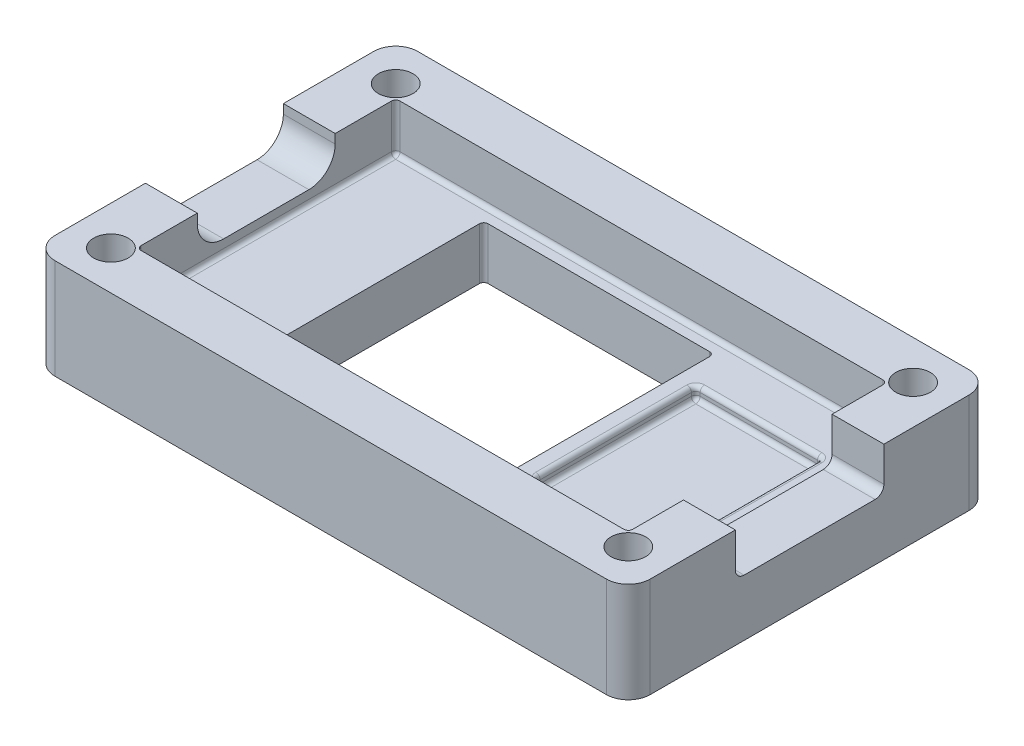
SolidWorks part; units mm, degrees
material "ABS"
ref_plane "Front Plane" through (0, 0, 0) normal (0, 0, 1) x (1, 0, 0)
ref_plane "Top Plane" through (0, 0, 0) normal (0, 1, 0) x (1, 0, 0)
ref_plane "Right Plane" through (0, 0, 0) normal (1, 0, 0) x (0, 0, -1)
sketch "Sketch1" plane through (0, 0, 0) normal (0, 1, 0) x (1, 0, 0)
  line L1 (-17.224, -10.493) -> (17.224, -10.493)
  line L2 (-17.224, -10.493) -> (-17.224, 10.493)
  line L3 (-17.224, 10.493) -> (17.224, 10.493)
  line L4 (17.224, -10.493) -> (17.224, 10.493)
  line L5 (-17.224, -10.493) -> (17.224, 10.493) construction
  line L6 (-17.224, 10.493) -> (17.224, -10.493) construction
  point P0 (0, 0)
  dimension "D1" = 20.986
  dimension "D2" = 34.448
extrude "Boss-Extrude1" add sketch "Sketch1" along normal blind 5.794
sketch "Sketch2" plane through (0, 5.794, 0) normal (0, 1, 0) x (1, 0, 0)
  line L1 (-14.224, -7.493) -> (14.224, -7.493)
  line L2 (-14.224, -7.493) -> (-14.224, 7.493)
  line L3 (-14.224, 7.493) -> (14.224, 7.493)
  line L4 (14.224, -7.493) -> (14.224, 7.493)
  line L5 (-14.224, -7.493) -> (14.224, 7.493) construction
  line L6 (-14.224, 7.493) -> (14.224, -7.493) construction
  point P0 (0, 0)
  dimension "D1" = 14.986
  dimension "D2" = 28.448
extrude "Cut-Extrude1" cut sketch "Sketch2" against normal blind 2.794
fillet "Fillet4" radius 0.254 4 edges at (14.224, 4.397, 7.493) (-14.224, 4.397, 7.493) (14.224, 4.397, -7.493) (-14.224, 4.397, -7.493)
sketch "Sketch3" plane through (17.224, 0, 0) normal (1, 0, 0) x (0, 0, -1)
  line L0 (-10.493, 5.794) -> (10.493, 5.794) construction
  line L1 (-4.2995, 5.794) -> (4.2995, 5.794)
  line L2 (-4.2995, 5.794) -> (-4.2995, 3.2749)
  line L3 (-4.2995, 3.2749) -> (4.2995, 3.2749)
  line L4 (4.2995, 5.794) -> (4.2995, 3.2749)
  line L5 (-10.493, 0) -> (10.493, 0) construction
  point P6 (0, 3.2749)
  point P11 (0, 0)
extrude "Cut-Extrude2" cut sketch "Sketch3" against normal up to surface (3 mm away) up to face at (14.224, 4.397, 0)
sketch "Sketch5" plane through (-17.224, 0, 0) normal (-1, 0, 0) x (0, 0, 1)
  line L0 (-3.9914, 5.794) -> (3.9914, 5.794)
  line L1 (-10.493, 5.794) -> (10.493, 5.794) construction
  line L2 (-10.493, 0) -> (10.493, 0) construction
  line L3 (-3.9914, 3.7403) -> (3.9914, 3.7403)
  line L4 (3.9914, 3.7403) -> (3.9914, 5.794)
  line L5 (-3.9914, 5.794) -> (-3.9914, 3.7403)
  point P4 (0, 5.794)
  point P7 (0, 0)
  point P8 (0, 3.7403)
extrude "Cut-Extrude3" cut sketch "Sketch5" against normal up to surface (3 mm away) up to face at (-14.224, 4.397, 0)
fillet "Fillet1" radius 1.524 2 edges at (-15.724, 3.7403, 3.9914) (-15.724, 3.7403, -3.9914)
fillet "Fillet2" radius 0.508 2 edges at (15.724, 3.2749, -4.2995) (15.724, 3.2749, 4.2995)
fillet "Fillet3" radius 1.27 4 edges at (-17.224, 2.897, -10.493) (-17.224, 2.897, 10.493) (17.224, 2.897, 10.493) (17.224, 2.897, -10.493)
fillet "Fillet5" radius 0.254 8 edges at (-14.1496, 3, 7.4186) (-14.224, 3, 0) (-14.1496, 3, -7.4186) (0, 3, -7.493) (14.1496, 3, -7.4186) (14.224, 3, 0) (14.1496, 3, 7.4186) (0, 3, 7.493)
sketch "Sketch10" plane through (0, 5.794, -5.794) normal (0, -1, 0) x (-1, 0, 0)
  circle A0 centre (-14.9721, 2.4471) radius 1
  circle A2 centre (14.9721, 2.4471) radius 1
  circle A3 centre (14.9721, -14.0351) radius 1
  circle A4 centre (-14.9721, -14.0351) radius 1
  circle A8 centre (14.9721, -14.0351) radius 1 construction
  circle A9 centre (14.9721, 2.4471) radius 1 construction
  circle A10 centre (-14.9721, 2.4471) radius 1 construction
  circle A11 centre (-14.9721, -14.0351) radius 1 construction
extrude "Cut-Extrude4" cut sketch "Sketch10" along normal blind 4.54
sketch "Sketch11" plane through (0, 0, 0) normal (0, -1, 0) x (1, 0, 0)
  line L0 (4.499, -6.1851) -> (-7.821, -6.1851) construction
  line L1 (-7.821, -6.1851) -> (4.499, -6.1851) construction
  line L2 (-7.821, -6.1851) -> (-7.821, 6.1349) construction
  line L3 (-7.821, 6.1349) -> (4.499, 6.1349) construction
  line L4 (4.499, -6.1851) -> (4.499, 6.1349) construction
  line L5 (4.499, 6.1349) -> (4.499, -6.1851) construction
  line L6 (-7.821, -6.1851) -> (4.499, 6.1349) construction
  line L7 (-8.321, -6.6851) -> (4.999, -6.6851)
  line L8 (-8.321, -6.6851) -> (-8.321, 6.6349)
  line L9 (-8.321, 6.6349) -> (4.999, 6.6349)
  line L10 (4.999, -6.6851) -> (4.999, 6.6349)
  line L11 (4.999, 6.6349) -> (-8.321, -6.6851) construction
  point P12 (-1.661, -0.0251)
  point P13 (-1.661, -0.0251)
  dimension "D1" = 0.5
extrude "Cut-Extrude5" cut sketch "Sketch11" against normal through all
fillet "Fillet6" radius 0.254 4 edges at (-8.321, 1.5, -6.6851) (4.999, 1.5, -6.6851) (4.999, 1.5, 6.6349) (-8.321, 1.5, 6.6349)
sketch "Sketch12" plane through (0, 3, 0) normal (0, 1, 0) x (1, 0, 0)
  line L0 (7.1583, -4.141) -> (7.1583, -4.641) construction
  line L1 (6.5162, 4.119) -> (12.8167, 4.119) construction
  line L2 (6.5162, 4.119) -> (6.5162, -4.141) construction
  line L3 (6.5162, -4.141) -> (12.8167, -4.141) construction
  line L4 (12.8167, 4.119) -> (12.8167, -4.141) construction
  line L6 (6.0162, 4.619) -> (13.3167, 4.619)
  line L7 (6.0162, 4.619) -> (6.0162, -4.641)
  line L8 (6.0162, -4.641) -> (13.3167, -4.641)
  line L9 (13.3167, 4.619) -> (13.3167, -4.641)
  line L10 (8.0096, 4.119) -> (8.0096, 4.619) construction
  line L11 (6.5162, 0.4683) -> (6.0162, 0.4683) construction
  line L12 (12.8167, 0.5902) -> (13.3167, 0.5902) construction
  dimension "D1" = 0.5
extrude "Cut-Extrude6" cut sketch "Sketch12" against normal blind 0.7
fillet "Fillet7" radius 0.254 12 edges at (13.3167, 2.65, -4.619) (13.3167, 2.65, 4.641) (9.6664, 2.3, -4.619) (13.3167, 2.3, 0.011) (9.6664, 2.3, 4.641) (6.0162, 2.65, 4.641) (6.0162, 2.3, 0.011) (6.0162, 2.65, -4.619) (13.3167, 3, 0.011) (6.0162, 3, 0.011) (9.6664, 3, 4.641) (9.6664, 3, -4.619)
equation "\"width\"=0.59"
equation "\"D1@Sketch2\"=\"width\""
equation "\"D1@Sketch1\"=\"width\"+6mm"
equation "\"height\"=1.12"
equation "\"D2@Sketch2\"=\"height\""
equation "\"D2@Sketch1\"=\"height\" + 6mm"
